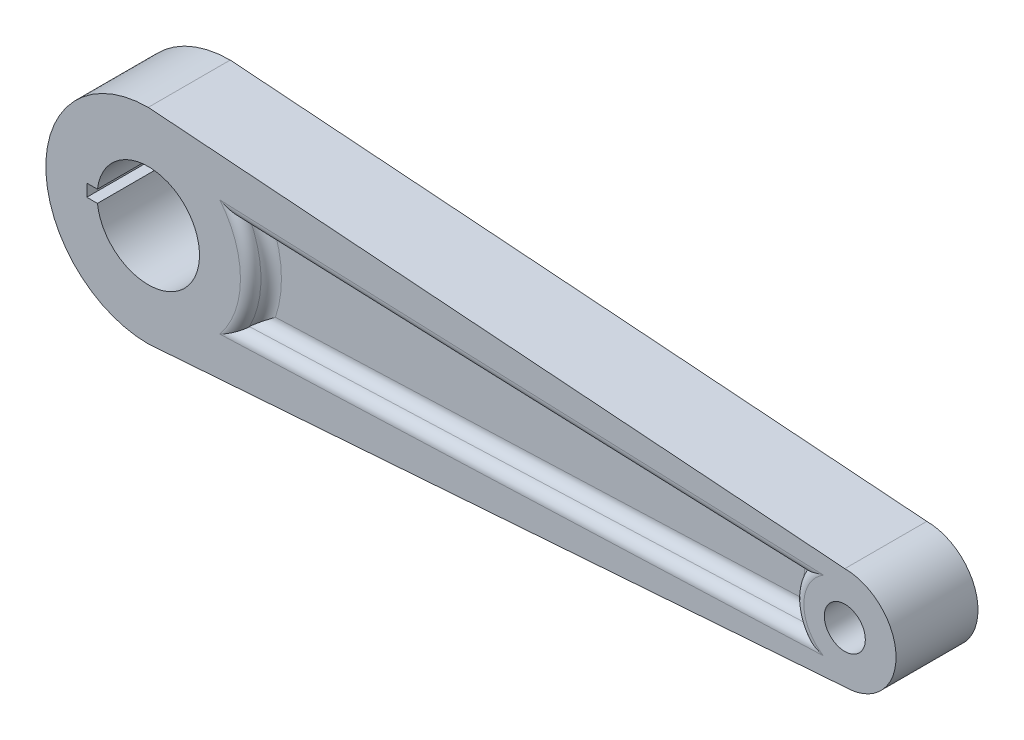
SolidWorks part; units mm, degrees
ref_plane "Front Plane" through (0, 0, 0) normal (0, 0, 1) x (1, 0, 0)
ref_plane "Top Plane" through (0, 0, 0) normal (0, 1, 0) x (1, 0, 0)
ref_plane "Right Plane" through (0, 0, 0) normal (1, 0, 0) x (0, 0, -1)
sketch "Sketch1" plane through (0, 0, 0) normal (0, 0, 1) x (1, 0, 0)
  line L0 (0, 50) -> (340, 25)
  line L1 (0, -50) -> (340, -25)
  circle A0 centre (0, 0) radius 25
  arc A1 (7.3134, 49.4622) -> (7.3134, -49.4622) centre (0, 0) ccw
  circle A2 centre (340, 0) radius 10
  arc A3 (340, -25) -> (340, 25) centre (340, 0) ccw
  dimension "D1" = 50
  dimension "D2" = 100
  dimension "D3" = 20
  dimension "D4" = 50
  dimension "D5" = 340
extrude "Boss-Extrude1" add sketch "Sketch1" along normal blind 20 contours L1 A3 L0 A1 A0 A2 region at (142.4544, 0, 0)
sketch "Sketch3" plane through (0, 0, 20) normal (0, 0, 1) x (1, 0, 0)
  line L0 (44.3959, 23) -> (318.3494, 12.5)
  line L1 (44.3959, -23) -> (318.3494, -12.5)
  arc A0 (44.3959, -23) -> (44.3959, 23) centre (0, 0) ccw
  arc A1 (318.3494, 12.5) -> (318.3494, -12.5) centre (340, 0) ccw
  arc A2 (0, 50) -> (0, -50) centre (0, 0) ccw construction
  arc A3 (340, -25) -> (340, 25) centre (340, 0) ccw construction
  dimension "D1" = 46
  dimension "D2" = 23
  dimension "D3" = 25
  dimension "D4" = 12.5
extrude "Cut-Extrude1" cut sketch "Sketch3" against normal blind 10
fillet "Fillet1" radius 5 8 edges at (315, 0, 20) (315, 0, 10) (50, 0, 20) (50, 0, 10) (181.3727, -17.75, 10) (181.3727, 17.75, 10) (181.3727, -17.75, 20) (181.3727, 17.75, 20)
mirror "Mirror1" about plane through (0, 0, 0) normal (0, 0, 1) of "Fillet1", "Cut-Extrude1", "Boss-Extrude1"
sketch "Sketch6" plane through (0, 0, 20) normal (0, 0, 1) x (1, 0, 0)
  line L1 (-30, 3) -> (-24.8193, 3)
  line L2 (-30, 3) -> (-30, -3)
  line L3 (-30, -3) -> (-24.8193, -3)
  circle A0 centre (0, 0) radius 25 construction
  arc A1 (-24.8193, 3) -> (-24.8193, -3) centre (0, 0) ccw
  dimension "D1" = 6
  dimension "D2" = 3
  dimension "D3" = 30
extrude "Cut-Extrude2" cut sketch "Sketch6" against normal through all
